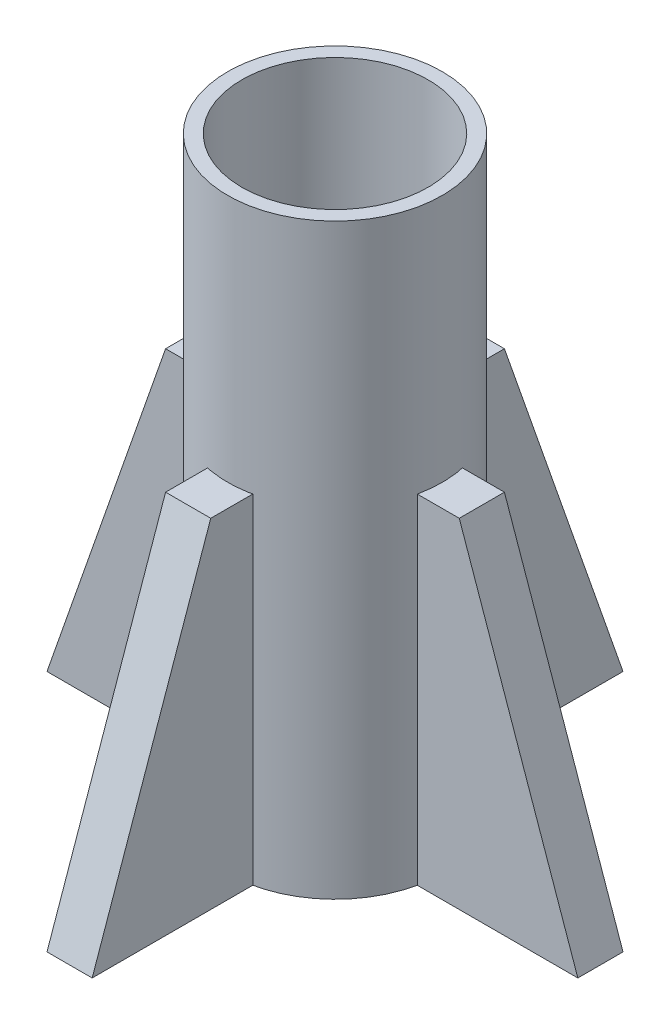
SolidWorks part; units mm, degrees
ref_plane "Front Plane" through (0, 0, 0) normal (0, 0, 1) x (1, 0, 0)
ref_plane "Top Plane" through (0, 0, 0) normal (0, 1, 0) x (1, 0, 0)
ref_plane "Right Plane" through (0, 0, 0) normal (1, 0, 0) x (0, 0, -1)
sketch "Sketch1" plane through (0, 0, 0) normal (0, 1, 0) x (1, 0, 0)
  circle A0 centre (0, 0) radius 9.5
  dimension "D1" = 19
extrude "Boss-Extrude1" add sketch "Sketch1" along normal blind 52
sketch "Sketch2" plane through (0, 52, 0) normal (0, 1, 0) x (1, 0, 0)
  circle A0 centre (0, 0) radius 8.25
  dimension "D1" = 16.5
extrude "Cut-Extrude1" cut sketch "Sketch2" against normal blind 50
sketch "Sketch3" plane through (0, 0, 0) normal (1, 0, 0) x (0, 0, -1)
  line L2 (-13, 30) -> (-23.5, 0)
  line L6 (23.5, 0) -> (13, 30)
  line L10 (-8.5, 0) -> (-8.5, 30)
  line L11 (-9.5, 0) -> (9.5, 0) construction
  line L12 (-9.5, 52) -> (-9.5, 0) construction
  line L13 (-13, 30) -> (-8.5, 30)
  line L14 (-23.5, 0) -> (-8.5, 0)
  line L15 (13, 30) -> (8.5, 30)
  line L16 (8.5, 30) -> (8.5, 0)
  line L17 (8.5, 0) -> (23.5, 0)
  line L19 (9.5, 0) -> (9.5, 52) construction
  dimension "D1" = 4.5
  dimension "D2" = 1
  dimension "D3" = 15
  dimension "D4" = 15
  dimension "D5" = 4.5
  dimension "D6" = 1
extrude "Boss-Extrude2" add sketch "Sketch3" along normal blind 2 and the other way blind 2 separate body
sketch "Sketch4" plane through (0, 0, 0) normal (0, 0, 1) x (1, 0, 0)
  line L2 (13, 30) -> (23.5, 0)
  line L8 (-23.5, 0) -> (-13, 30)
  line L10 (23.5, 0) -> (8.5, 0)
  line L11 (-9.5, 0) -> (9.5, 0) construction
  line L12 (8.5, 0) -> (8.5, 30)
  line L13 (8.5, 30) -> (13, 30)
  line L14 (-13, 30) -> (-8.5, 30)
  line L15 (-8.5, 30) -> (-8.5, 0)
  line L16 (-8.5, 0) -> (-23.5, 0)
  line L17 (-9.5, 52) -> (-9.5, 0) construction
  line L18 (9.5, 0) -> (9.5, 52) construction
  dimension "D1" = 4.5
  dimension "D2" = 15
  dimension "D3" = 1
  dimension "D4" = 1
  dimension "D5" = 15
  dimension "D6" = 4.5
extrude "Boss-Extrude3" add sketch "Sketch4" along normal blind 2 and the other way blind 2 separate body
